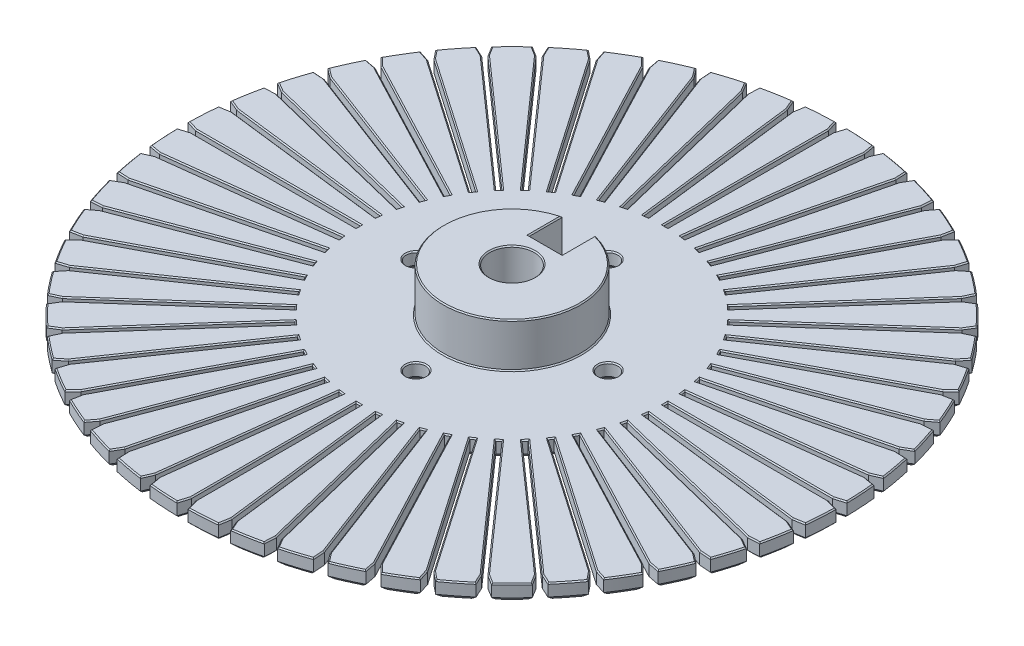
SolidWorks part; units mm, degrees
ref_plane "Ebene vorne" through (0, 0, 0) normal (0, 0, 1) x (1, 0, 0)
ref_plane "Ebene oben" through (0, 0, 0) normal (0, 1, 0) x (1, 0, 0)
ref_plane "Ebene rechts" through (0, 0, 0) normal (1, 0, 0) x (0, 0, -1)
sketch "Skizze1" plane through (0, 0, 0) normal (0, 1, 0) x (1, 0, 0)
  circle A0 centre (0, 0) radius 60
  dimension "D1" = 120
extrude "Aufsatz-Linear austragen1" add sketch "Skizze1" along normal blind 3
sketch "Skizze2" plane through (0, 3, 0) normal (0, 1, 0) x (1, 0, 0)
  line L0 (0, 0) -> (64.8042, 0) construction
  line L1 (27.9917, 0.4) -> (27.9917, -0.4)
  line L2 (27.9917, -0.4) -> (57.9917, -0.4)
  line L3 (57.9917, -0.4) -> (59.9917, -1)
  line L4 (27.9917, 0.4) -> (57.9917, 0.4)
  line L5 (57.9917, 0.4) -> (59.9917, 1)
  line L6 (0, 0) -> (64.3317, -7.8113) construction
  line L7 (27.8358, -2.9769) -> (27.7394, -3.7711)
  line L8 (27.8358, -2.9769) -> (57.6171, -6.593)
  line L9 (27.7394, -3.7711) -> (57.5206, -7.3872)
  line L10 (57.5206, -7.3872) -> (59.4337, -8.2239)
  line L11 (57.6171, -6.593) -> (59.6748, -6.2385)
  line L12 (0, 0) -> (62.9211, -15.5086) construction
  line L13 (27.274, -6.3105) -> (27.0826, -7.0872)
  line L14 (27.274, -6.3105) -> (56.4023, -13.4899)
  line L15 (27.0826, -7.0872) -> (56.2108, -14.2667)
  line L16 (56.2108, -14.2667) -> (58.0091, -15.3279)
  line L17 (56.4023, -13.4899) -> (58.4877, -13.386)
  line L18 (0, 0) -> (60.5929, -22.9799) construction
  line L19 (26.3145, -9.552) -> (26.0308, -10.3)
  line L20 (26.3145, -9.552) -> (54.365, -20.1901)
  line L21 (26.0308, -10.3) -> (54.0813, -20.9381)
  line L22 (54.0813, -20.9381) -> (55.7386, -22.2084)
  line L23 (54.365, -20.1901) -> (56.4478, -20.3383)
  line L24 (0, 0) -> (57.3812, -30.116) construction
  line L25 (24.9713, -12.6542) -> (24.5995, -13.3626)
  line L26 (24.9713, -12.6542) -> (51.535, -26.5959)
  line L27 (24.5995, -13.3626) -> (51.1632, -27.3043)
  line L28 (51.1632, -27.3043) -> (52.6553, -28.765)
  line L29 (51.535, -26.5959) -> (53.5847, -26.9941)
  line L30 (0, 0) -> (53.3328, -36.813) construction
  line L31 (23.2639, -15.5719) -> (22.8095, -16.2303)
  line L32 (23.2639, -15.5719) -> (47.9534, -32.6138)
  line L33 (22.8095, -16.2303) -> (47.499, -33.2722)
  line L34 (47.499, -33.2722) -> (48.8041, -34.9021)
  line L35 (47.9534, -32.6138) -> (49.9402, -33.2562)
  line L36 (0, 0) -> (48.5066, -42.9731) construction
  line L37 (21.2173, -18.2625) -> (20.6868, -18.8613)
  line L38 (21.2173, -18.2625) -> (43.6726, -38.1562)
  line L39 (20.6868, -18.8613) -> (43.1421, -38.755)
  line L40 (43.1421, -38.755) -> (44.2413, -40.5303)
  line L41 (43.6726, -38.1562) -> (45.5675, -39.0333)
  line L42 (0, 0) -> (42.9731, -48.5066) construction
  line L43 (18.8613, -20.6868) -> (18.2625, -21.2173)
  line L44 (18.8613, -20.6868) -> (38.755, -43.1421)
  line L45 (18.2625, -21.2173) -> (38.1562, -43.6726)
  line L46 (38.1562, -43.6726) -> (39.0333, -45.5675)
  line L47 (38.755, -43.1421) -> (40.5303, -44.2413)
  line L48 (0, 0) -> (36.813, -53.3328) construction
  line L49 (16.2303, -22.8095) -> (15.5719, -23.2639)
  line L50 (16.2303, -22.8095) -> (33.2722, -47.499)
  line L51 (15.5719, -23.2639) -> (32.6138, -47.9534)
  line L52 (32.6138, -47.9534) -> (33.2562, -49.9402)
  line L53 (33.2722, -47.499) -> (34.9021, -48.8041)
  line L54 (0, 0) -> (30.116, -57.3812) construction
  line L55 (13.3626, -24.5995) -> (12.6542, -24.9713)
  line L56 (13.3626, -24.5995) -> (27.3043, -51.1632)
  line L57 (12.6542, -24.9713) -> (26.5959, -51.535)
  line L58 (26.5959, -51.535) -> (26.9941, -53.5847)
  line L59 (27.3043, -51.1632) -> (28.765, -52.6553)
  line L60 (0, 0) -> (22.9799, -60.5929) construction
  line L61 (10.3, -26.0308) -> (9.552, -26.3145)
  line L62 (10.3, -26.0308) -> (20.9381, -54.0813)
  line L63 (9.552, -26.3145) -> (20.1901, -54.365)
  line L64 (20.1901, -54.365) -> (20.3383, -56.4478)
  line L65 (20.9381, -54.0813) -> (22.2084, -55.7386)
  line L66 (0, 0) -> (15.5086, -62.9211) construction
  line L67 (7.0872, -27.0826) -> (6.3105, -27.274)
  line L68 (7.0872, -27.0826) -> (14.2667, -56.2108)
  line L69 (6.3105, -27.274) -> (13.4899, -56.4023)
  line L70 (13.4899, -56.4023) -> (13.386, -58.4877)
  line L71 (14.2667, -56.2108) -> (15.3279, -58.0091)
  line L72 (0, 0) -> (7.8113, -64.3317) construction
  line L73 (3.7711, -27.7394) -> (2.9769, -27.8358)
  line L74 (3.7711, -27.7394) -> (7.3872, -57.5206)
  line L75 (2.9769, -27.8358) -> (6.593, -57.6171)
  line L76 (6.593, -57.6171) -> (6.2385, -59.6748)
  line L77 (7.3872, -57.5206) -> (8.2239, -59.4337)
  line L78 (0, 0) -> (0, -64.8042) construction
  line L79 (0.4, -27.9917) -> (-0.4, -27.9917)
  line L80 (0.4, -27.9917) -> (0.4, -57.9917)
  line L81 (-0.4, -27.9917) -> (-0.4, -57.9917)
  line L82 (-0.4, -57.9917) -> (-1, -59.9917)
  line L83 (0.4, -57.9917) -> (1, -59.9917)
  line L84 (0, 0) -> (-7.8113, -64.3317) construction
  line L85 (-2.9769, -27.8358) -> (-3.7711, -27.7394)
  line L86 (-2.9769, -27.8358) -> (-6.593, -57.6171)
  line L87 (-3.7711, -27.7394) -> (-7.3872, -57.5206)
  line L88 (-7.3872, -57.5206) -> (-8.2239, -59.4337)
  line L89 (-6.593, -57.6171) -> (-6.2385, -59.6748)
  line L90 (0, 0) -> (-15.5086, -62.9211) construction
  line L91 (-6.3105, -27.274) -> (-7.0872, -27.0826)
  line L92 (-6.3105, -27.274) -> (-13.4899, -56.4023)
  line L93 (-7.0872, -27.0826) -> (-14.2667, -56.2108)
  line L94 (-14.2667, -56.2108) -> (-15.3279, -58.0091)
  line L95 (-13.4899, -56.4023) -> (-13.386, -58.4877)
  line L96 (0, 0) -> (-22.9799, -60.5929) construction
  line L97 (-9.552, -26.3145) -> (-10.3, -26.0308)
  line L98 (-9.552, -26.3145) -> (-20.1901, -54.365)
  line L99 (-10.3, -26.0308) -> (-20.9381, -54.0813)
  line L100 (-20.9381, -54.0813) -> (-22.2084, -55.7386)
  line L101 (-20.1901, -54.365) -> (-20.3383, -56.4478)
  line L102 (0, 0) -> (-30.116, -57.3812) construction
  line L103 (-12.6542, -24.9713) -> (-13.3626, -24.5995)
  line L104 (-12.6542, -24.9713) -> (-26.5959, -51.535)
  line L105 (-13.3626, -24.5995) -> (-27.3043, -51.1632)
  line L106 (-27.3043, -51.1632) -> (-28.765, -52.6553)
  line L107 (-26.5959, -51.535) -> (-26.9941, -53.5847)
  line L108 (0, 0) -> (-36.813, -53.3328) construction
  line L109 (-15.5719, -23.2639) -> (-16.2303, -22.8095)
  line L110 (-15.5719, -23.2639) -> (-32.6138, -47.9534)
  line L111 (-16.2303, -22.8095) -> (-33.2722, -47.499)
  line L112 (-33.2722, -47.499) -> (-34.9021, -48.8041)
  line L113 (-32.6138, -47.9534) -> (-33.2562, -49.9402)
  line L114 (0, 0) -> (-42.9731, -48.5066) construction
  line L115 (-18.2625, -21.2173) -> (-18.8613, -20.6868)
  line L116 (-18.2625, -21.2173) -> (-38.1562, -43.6726)
  line L117 (-18.8613, -20.6868) -> (-38.755, -43.1421)
  line L118 (-38.755, -43.1421) -> (-40.5303, -44.2413)
  line L119 (-38.1562, -43.6726) -> (-39.0333, -45.5675)
  line L120 (0, 0) -> (-48.5066, -42.9731) construction
  line L121 (-20.6868, -18.8613) -> (-21.2173, -18.2625)
  line L122 (-20.6868, -18.8613) -> (-43.1421, -38.755)
  line L123 (-21.2173, -18.2625) -> (-43.6726, -38.1562)
  line L124 (-43.6726, -38.1562) -> (-45.5675, -39.0333)
  line L125 (-43.1421, -38.755) -> (-44.2413, -40.5303)
  line L126 (0, 0) -> (-53.3328, -36.813) construction
  line L127 (-22.8095, -16.2303) -> (-23.2639, -15.5719)
  line L128 (-22.8095, -16.2303) -> (-47.499, -33.2722)
  line L129 (-23.2639, -15.5719) -> (-47.9534, -32.6138)
  line L130 (-47.9534, -32.6138) -> (-49.9402, -33.2562)
  line L131 (-47.499, -33.2722) -> (-48.8041, -34.9021)
  line L132 (0, 0) -> (-57.3812, -30.116) construction
  line L133 (-24.5995, -13.3626) -> (-24.9713, -12.6542)
  line L134 (-24.5995, -13.3626) -> (-51.1632, -27.3043)
  line L135 (-24.9713, -12.6542) -> (-51.535, -26.5959)
  line L136 (-51.535, -26.5959) -> (-53.5847, -26.9941)
  line L137 (-51.1632, -27.3043) -> (-52.6553, -28.765)
  line L138 (0, 0) -> (-60.5929, -22.9799) construction
  line L139 (-26.0308, -10.3) -> (-26.3145, -9.552)
  line L140 (-26.0308, -10.3) -> (-54.0813, -20.9381)
  line L141 (-26.3145, -9.552) -> (-54.365, -20.1901)
  line L142 (-54.365, -20.1901) -> (-56.4478, -20.3383)
  line L143 (-54.0813, -20.9381) -> (-55.7386, -22.2084)
  line L144 (0, 0) -> (-62.9211, -15.5086) construction
  line L145 (-27.0826, -7.0872) -> (-27.274, -6.3105)
  line L146 (-27.0826, -7.0872) -> (-56.2108, -14.2667)
  line L147 (-27.274, -6.3105) -> (-56.4023, -13.4899)
  line L148 (-56.4023, -13.4899) -> (-58.4877, -13.386)
  line L149 (-56.2108, -14.2667) -> (-58.0091, -15.3279)
  line L150 (0, 0) -> (-64.3317, -7.8113) construction
  line L151 (-27.7394, -3.7711) -> (-27.8358, -2.9769)
  line L152 (-27.7394, -3.7711) -> (-57.5206, -7.3872)
  line L153 (-27.8358, -2.9769) -> (-57.6171, -6.593)
  line L154 (-57.6171, -6.593) -> (-59.6748, -6.2385)
  line L155 (-57.5206, -7.3872) -> (-59.4337, -8.2239)
  line L156 (0, 0) -> (-64.8042, 0) construction
  line L157 (-27.9917, -0.4) -> (-27.9917, 0.4)
  line L158 (-27.9917, -0.4) -> (-57.9917, -0.4)
  line L159 (-27.9917, 0.4) -> (-57.9917, 0.4)
  line L160 (-57.9917, 0.4) -> (-59.9917, 1)
  line L161 (-57.9917, -0.4) -> (-59.9917, -1)
  line L162 (0, 0) -> (-64.3317, 7.8113) construction
  line L163 (-27.8358, 2.9769) -> (-27.7394, 3.7711)
  line L164 (-27.8358, 2.9769) -> (-57.6171, 6.593)
  line L165 (-27.7394, 3.7711) -> (-57.5206, 7.3872)
  line L166 (-57.5206, 7.3872) -> (-59.4337, 8.2239)
  line L167 (-57.6171, 6.593) -> (-59.6748, 6.2385)
  line L168 (0, 0) -> (-62.9211, 15.5086) construction
  line L169 (-27.274, 6.3105) -> (-27.0826, 7.0872)
  line L170 (-27.274, 6.3105) -> (-56.4023, 13.4899)
  line L171 (-27.0826, 7.0872) -> (-56.2108, 14.2667)
  line L172 (-56.2108, 14.2667) -> (-58.0091, 15.3279)
  line L173 (-56.4023, 13.4899) -> (-58.4877, 13.386)
  line L174 (0, 0) -> (-60.5929, 22.9799) construction
  line L175 (-26.3145, 9.552) -> (-26.0308, 10.3)
  line L176 (-26.3145, 9.552) -> (-54.365, 20.1901)
  line L177 (-26.0308, 10.3) -> (-54.0813, 20.9381)
  line L178 (-54.0813, 20.9381) -> (-55.7386, 22.2084)
  line L179 (-54.365, 20.1901) -> (-56.4478, 20.3383)
  line L180 (0, 0) -> (-57.3812, 30.116) construction
  line L181 (-24.9713, 12.6542) -> (-24.5995, 13.3626)
  line L182 (-24.9713, 12.6542) -> (-51.535, 26.5959)
  line L183 (-24.5995, 13.3626) -> (-51.1632, 27.3043)
  line L184 (-51.1632, 27.3043) -> (-52.6553, 28.765)
  line L185 (-51.535, 26.5959) -> (-53.5847, 26.9941)
  line L186 (0, 0) -> (-53.3328, 36.813) construction
  line L187 (-23.2639, 15.5719) -> (-22.8095, 16.2303)
  line L188 (-23.2639, 15.5719) -> (-47.9534, 32.6138)
  line L189 (-22.8095, 16.2303) -> (-47.499, 33.2722)
  line L190 (-47.499, 33.2722) -> (-48.8041, 34.9021)
  line L191 (-47.9534, 32.6138) -> (-49.9402, 33.2562)
  line L192 (0, 0) -> (-48.5066, 42.9731) construction
  line L193 (-21.2173, 18.2625) -> (-20.6868, 18.8613)
  line L194 (-21.2173, 18.2625) -> (-43.6726, 38.1562)
  line L195 (-20.6868, 18.8613) -> (-43.1421, 38.755)
  line L196 (-43.1421, 38.755) -> (-44.2413, 40.5303)
  line L197 (-43.6726, 38.1562) -> (-45.5675, 39.0333)
  line L198 (0, 0) -> (-42.9731, 48.5066) construction
  line L199 (-18.8613, 20.6868) -> (-18.2625, 21.2173)
  line L200 (-18.8613, 20.6868) -> (-38.755, 43.1421)
  line L201 (-18.2625, 21.2173) -> (-38.1562, 43.6726)
  line L202 (-38.1562, 43.6726) -> (-39.0333, 45.5675)
  line L203 (-38.755, 43.1421) -> (-40.5303, 44.2413)
  line L204 (0, 0) -> (-36.813, 53.3328) construction
  line L205 (-16.2303, 22.8095) -> (-15.5719, 23.2639)
  line L206 (-16.2303, 22.8095) -> (-33.2722, 47.499)
  line L207 (-15.5719, 23.2639) -> (-32.6138, 47.9534)
  line L208 (-32.6138, 47.9534) -> (-33.2562, 49.9402)
  line L209 (-33.2722, 47.499) -> (-34.9021, 48.8041)
  line L210 (0, 0) -> (-30.116, 57.3812) construction
  line L211 (-13.3626, 24.5995) -> (-12.6542, 24.9713)
  line L212 (-13.3626, 24.5995) -> (-27.3043, 51.1632)
  line L213 (-12.6542, 24.9713) -> (-26.5959, 51.535)
  line L214 (-26.5959, 51.535) -> (-26.9941, 53.5847)
  line L215 (-27.3043, 51.1632) -> (-28.765, 52.6553)
  line L216 (0, 0) -> (-22.9799, 60.5929) construction
  line L217 (-10.3, 26.0308) -> (-9.552, 26.3145)
  line L218 (-10.3, 26.0308) -> (-20.9381, 54.0813)
  line L219 (-9.552, 26.3145) -> (-20.1901, 54.365)
  line L220 (-20.1901, 54.365) -> (-20.3383, 56.4478)
  line L221 (-20.9381, 54.0813) -> (-22.2084, 55.7386)
  line L222 (0, 0) -> (-15.5086, 62.9211) construction
  line L223 (-7.0872, 27.0826) -> (-6.3105, 27.274)
  line L224 (-7.0872, 27.0826) -> (-14.2667, 56.2108)
  line L225 (-6.3105, 27.274) -> (-13.4899, 56.4023)
  line L226 (-13.4899, 56.4023) -> (-13.386, 58.4877)
  line L227 (-14.2667, 56.2108) -> (-15.3279, 58.0091)
  line L228 (0, 0) -> (-7.8113, 64.3317) construction
  line L229 (-3.7711, 27.7394) -> (-2.9769, 27.8358)
  line L230 (-3.7711, 27.7394) -> (-7.3872, 57.5206)
  line L231 (-2.9769, 27.8358) -> (-6.593, 57.6171)
  line L232 (-6.593, 57.6171) -> (-6.2385, 59.6748)
  line L233 (-7.3872, 57.5206) -> (-8.2239, 59.4337)
  line L234 (0, 0) -> (0, 64.8042) construction
  line L235 (-0.4, 27.9917) -> (0.4, 27.9917)
  line L236 (-0.4, 27.9917) -> (-0.4, 57.9917)
  line L237 (0.4, 27.9917) -> (0.4, 57.9917)
  line L238 (0.4, 57.9917) -> (1, 59.9917)
  line L239 (-0.4, 57.9917) -> (-1, 59.9917)
  line L240 (0, 0) -> (7.8113, 64.3317) construction
  line L241 (2.9769, 27.8358) -> (3.7711, 27.7394)
  line L242 (2.9769, 27.8358) -> (6.593, 57.6171)
  line L243 (3.7711, 27.7394) -> (7.3872, 57.5206)
  line L244 (7.3872, 57.5206) -> (8.2239, 59.4337)
  line L245 (6.593, 57.6171) -> (6.2385, 59.6748)
  line L246 (0, 0) -> (15.5086, 62.9211) construction
  line L247 (6.3105, 27.274) -> (7.0872, 27.0826)
  line L248 (6.3105, 27.274) -> (13.4899, 56.4023)
  line L249 (7.0872, 27.0826) -> (14.2667, 56.2108)
  line L250 (14.2667, 56.2108) -> (15.3279, 58.0091)
  line L251 (13.4899, 56.4023) -> (13.386, 58.4877)
  line L252 (0, 0) -> (22.9799, 60.5929) construction
  line L253 (9.552, 26.3145) -> (10.3, 26.0308)
  line L254 (9.552, 26.3145) -> (20.1901, 54.365)
  line L255 (10.3, 26.0308) -> (20.9381, 54.0813)
  line L256 (20.9381, 54.0813) -> (22.2084, 55.7386)
  line L257 (20.1901, 54.365) -> (20.3383, 56.4478)
  line L258 (0, 0) -> (30.116, 57.3812) construction
  line L259 (12.6542, 24.9713) -> (13.3626, 24.5995)
  line L260 (12.6542, 24.9713) -> (26.5959, 51.535)
  line L261 (13.3626, 24.5995) -> (27.3043, 51.1632)
  line L262 (27.3043, 51.1632) -> (28.765, 52.6553)
  line L263 (26.5959, 51.535) -> (26.9941, 53.5847)
  line L264 (0, 0) -> (36.813, 53.3328) construction
  line L265 (15.5719, 23.2639) -> (16.2303, 22.8095)
  line L266 (15.5719, 23.2639) -> (32.6138, 47.9534)
  line L267 (16.2303, 22.8095) -> (33.2722, 47.499)
  line L268 (33.2722, 47.499) -> (34.9021, 48.8041)
  line L269 (32.6138, 47.9534) -> (33.2562, 49.9402)
  line L270 (0, 0) -> (42.9731, 48.5066) construction
  line L271 (18.2625, 21.2173) -> (18.8613, 20.6868)
  line L272 (18.2625, 21.2173) -> (38.1562, 43.6726)
  line L273 (18.8613, 20.6868) -> (38.755, 43.1421)
  line L274 (38.755, 43.1421) -> (40.5303, 44.2413)
  line L275 (38.1562, 43.6726) -> (39.0333, 45.5675)
  line L276 (0, 0) -> (48.5066, 42.9731) construction
  line L277 (20.6868, 18.8613) -> (21.2173, 18.2625)
  line L278 (20.6868, 18.8613) -> (43.1421, 38.755)
  line L279 (21.2173, 18.2625) -> (43.6726, 38.1562)
  line L280 (43.6726, 38.1562) -> (45.5675, 39.0333)
  line L281 (43.1421, 38.755) -> (44.2413, 40.5303)
  line L282 (0, 0) -> (53.3328, 36.813) construction
  line L283 (22.8095, 16.2303) -> (23.2639, 15.5719)
  line L284 (22.8095, 16.2303) -> (47.499, 33.2722)
  line L285 (23.2639, 15.5719) -> (47.9534, 32.6138)
  line L286 (47.9534, 32.6138) -> (49.9402, 33.2562)
  line L287 (47.499, 33.2722) -> (48.8041, 34.9021)
  line L288 (0, 0) -> (57.3812, 30.116) construction
  line L289 (24.5995, 13.3626) -> (24.9713, 12.6542)
  line L290 (24.5995, 13.3626) -> (51.1632, 27.3043)
  line L291 (24.9713, 12.6542) -> (51.535, 26.5959)
  line L292 (51.535, 26.5959) -> (53.5847, 26.9941)
  line L293 (51.1632, 27.3043) -> (52.6553, 28.765)
  line L294 (0, 0) -> (60.5929, 22.9799) construction
  line L295 (26.0308, 10.3) -> (26.3145, 9.552)
  line L296 (26.0308, 10.3) -> (54.0813, 20.9381)
  line L297 (26.3145, 9.552) -> (54.365, 20.1901)
  line L298 (54.365, 20.1901) -> (56.4478, 20.3383)
  line L299 (54.0813, 20.9381) -> (55.7386, 22.2084)
  line L300 (0, 0) -> (62.9211, 15.5086) construction
  line L301 (27.0826, 7.0872) -> (27.274, 6.3105)
  line L302 (27.0826, 7.0872) -> (56.2108, 14.2667)
  line L303 (27.274, 6.3105) -> (56.4023, 13.4899)
  line L304 (56.4023, 13.4899) -> (58.4877, 13.386)
  line L305 (56.2108, 14.2667) -> (58.0091, 15.3279)
  line L306 (0, 0) -> (64.3317, 7.8113) construction
  line L307 (27.7394, 3.7711) -> (27.8358, 2.9769)
  line L308 (27.7394, 3.7711) -> (57.5206, 7.3872)
  line L309 (27.8358, 2.9769) -> (57.6171, 6.593)
  line L310 (57.6171, 6.593) -> (59.6748, 6.2385)
  line L311 (57.5206, 7.3872) -> (59.4337, 8.2239)
  arc A0 (59.9917, 1) -> (59.9917, -1) centre (0, 0) cw
  circle A1 centre (0, 0) radius 60 construction
  arc A2 (59.6748, -6.2385) -> (59.4337, -8.2239) centre (0, 0) cw
  arc A3 (58.4877, -13.386) -> (58.0091, -15.3279) centre (0, 0) cw
  arc A4 (56.4478, -20.3383) -> (55.7386, -22.2084) centre (0, 0) cw
  arc A5 (53.5847, -26.9941) -> (52.6553, -28.765) centre (0, 0) cw
  arc A6 (49.9402, -33.2562) -> (48.8041, -34.9021) centre (0, 0) cw
  arc A7 (45.5675, -39.0333) -> (44.2413, -40.5303) centre (0, 0) cw
  arc A8 (40.5303, -44.2413) -> (39.0333, -45.5675) centre (0, 0) cw
  arc A9 (34.9021, -48.8041) -> (33.2562, -49.9402) centre (0, 0) cw
  arc A10 (28.765, -52.6553) -> (26.9941, -53.5847) centre (0, 0) cw
  arc A11 (22.2084, -55.7386) -> (20.3383, -56.4478) centre (0, 0) cw
  arc A12 (15.3279, -58.0091) -> (13.386, -58.4877) centre (0, 0) cw
  arc A13 (8.2239, -59.4337) -> (6.2385, -59.6748) centre (0, 0) cw
  arc A14 (1, -59.9917) -> (-1, -59.9917) centre (0, 0) cw
  arc A15 (-6.2385, -59.6748) -> (-8.2239, -59.4337) centre (0, 0) cw
  arc A16 (-13.386, -58.4877) -> (-15.3279, -58.0091) centre (0, 0) cw
  arc A17 (-20.3383, -56.4478) -> (-22.2084, -55.7386) centre (0, 0) cw
  arc A18 (-26.9941, -53.5847) -> (-28.765, -52.6553) centre (0, 0) cw
  arc A19 (-33.2562, -49.9402) -> (-34.9021, -48.8041) centre (0, 0) cw
  arc A20 (-39.0333, -45.5675) -> (-40.5303, -44.2413) centre (0, 0) cw
  arc A21 (-44.2413, -40.5303) -> (-45.5675, -39.0333) centre (0, 0) cw
  arc A22 (-48.8041, -34.9021) -> (-49.9402, -33.2562) centre (0, 0) cw
  arc A23 (-52.6553, -28.765) -> (-53.5847, -26.9941) centre (0, 0) cw
  arc A24 (-55.7386, -22.2084) -> (-56.4478, -20.3383) centre (0, 0) cw
  arc A25 (-58.0091, -15.3279) -> (-58.4877, -13.386) centre (0, 0) cw
  arc A26 (-59.4337, -8.2239) -> (-59.6748, -6.2385) centre (0, 0) cw
  arc A27 (-59.9917, -1) -> (-59.9917, 1) centre (0, 0) cw
  arc A28 (-59.6748, 6.2385) -> (-59.4337, 8.2239) centre (0, 0) cw
  arc A29 (-58.4877, 13.386) -> (-58.0091, 15.3279) centre (0, 0) cw
  arc A30 (-56.4478, 20.3383) -> (-55.7386, 22.2084) centre (0, 0) cw
  arc A31 (-53.5847, 26.9941) -> (-52.6553, 28.765) centre (0, 0) cw
  arc A32 (-49.9402, 33.2562) -> (-48.8041, 34.9021) centre (0, 0) cw
  arc A33 (-45.5675, 39.0333) -> (-44.2413, 40.5303) centre (0, 0) cw
  arc A34 (-40.5303, 44.2413) -> (-39.0333, 45.5675) centre (0, 0) cw
  arc A35 (-34.9021, 48.8041) -> (-33.2562, 49.9402) centre (0, 0) cw
  arc A36 (-28.765, 52.6553) -> (-26.9941, 53.5847) centre (0, 0) cw
  arc A37 (-22.2084, 55.7386) -> (-20.3383, 56.4478) centre (0, 0) cw
  arc A38 (-15.3279, 58.0091) -> (-13.386, 58.4877) centre (0, 0) cw
  arc A39 (-8.2239, 59.4337) -> (-6.2385, 59.6748) centre (0, 0) cw
  arc A40 (-1, 59.9917) -> (1, 59.9917) centre (0, 0) cw
  arc A41 (6.2385, 59.6748) -> (8.2239, 59.4337) centre (0, 0) cw
  arc A42 (13.386, 58.4877) -> (15.3279, 58.0091) centre (0, 0) cw
  arc A43 (20.3383, 56.4478) -> (22.2084, 55.7386) centre (0, 0) cw
  arc A44 (26.9941, 53.5847) -> (28.765, 52.6553) centre (0, 0) cw
  arc A45 (33.2562, 49.9402) -> (34.9021, 48.8041) centre (0, 0) cw
  arc A46 (39.0333, 45.5675) -> (40.5303, 44.2413) centre (0, 0) cw
  arc A47 (44.2413, 40.5303) -> (45.5675, 39.0333) centre (0, 0) cw
  arc A48 (48.8041, 34.9021) -> (49.9402, 33.2562) centre (0, 0) cw
  arc A49 (52.6553, 28.765) -> (53.5847, 26.9941) centre (0, 0) cw
  arc A50 (55.7386, 22.2084) -> (56.4478, 20.3383) centre (0, 0) cw
  arc A51 (58.0091, 15.3279) -> (58.4877, 13.386) centre (0, 0) cw
  arc A52 (59.4337, 8.2239) -> (59.6748, 6.2385) centre (0, 0) cw
  point P373 (0, 0)
  dimension "D5" = 52
  dimension "D1" = 0.8
  dimension "D2" = 30
  dimension "D3" = 2
  dimension "D4" = 2
extrude "Schnitt-Linear austragen1" cut sketch "Skizze2" against normal blind 5
sketch "Skizze3" plane through (0, 3, 0) normal (0, 1, 0) x (1, 0, 0)
  line L0 (0, 12.5) -> (0, 0) construction
  line L7 (-3, 12.1347) -> (-3, 6.1347)
  line L8 (-3, 6.1347) -> (3, 6.1347)
  line L9 (3, 6.1347) -> (3, 12.1347)
  arc A0 (-3, 12.1347) -> (3, 12.1347) centre (0, 0) ccw
  dimension "D1" = 25
  dimension "D2" = 6
  dimension "D3" = 6
extrude "Aufsatz-Linear austragen2" add sketch "Skizze3" along normal blind 8
sketch "Skizze4" plane through (0, 11, 0) normal (0, 1, 0) x (1, 0, 0)
  circle A0 centre (0, 0) radius 4.05
  dimension "D1" = 8.1
extrude "Schnitt-Linear austragen4" cut sketch "Skizze4" against normal through all
sketch "Skizze5" plane through (0, 3, 0) normal (0, 1, 0) x (1, 0, 0)
  circle A0 centre (0, 0) radius 17.5 construction
  circle A1 centre (0, 17.5) radius 1.75
  circle A2 centre (17.5, 0) radius 1.75
  circle A3 centre (-17.5, 0) radius 1.75
  circle A4 centre (0, -17.5) radius 1.75
  dimension "D1" = 3.5
  dimension "D2" = 35
extrude "Schnitt-Linear austragen5" cut sketch "Skizze5" against normal up to surface (3 mm away) up to face at (0, 0, 4.05)
chamfer "Fase1" distance 0.8 angle 45 317 edges at (27.7876, 0, -3.374) (42.63, 0, -5.5792) (58.4772, 0, -7.8056) (59.0172, 0, -10.8153) (57.445, 0, -13.438) (41.8381, 0, -9.9002) (27.1783, 0, -6.6988) (41.6467, 0, -10.677) (57.11, 0, -14.7973) (57.2833, 0, -17.8502) (55.4064, 0, -20.2642) (40.3397, 0, -14.871) (26.1727, 0, -9.926) (40.0561, 0, -15.6191) (54.9099, 0, -21.5732) (54.714, 0, -24.6248) (52.5598, 0, -26.795) (38.2531, 0, -19.625) (24.7854, 0, -13.0084) (37.8813, 0, -20.3334) (51.9092, 0, -28.0346) (51.3469, 0, -31.0403) (48.9468, 0, -32.935) (35.6087, 0, -24.0929) (23.0367, 0, -15.9011) (35.1542, 0, -24.7512) (48.1515, 0, -34.0872) (47.231, 0, -37.0031) (44.6201, 0, -38.5948) (32.445, 0, -28.2093) (20.9521, 0, -18.5619) (31.9145, 0, -28.8082) (43.6917, 0, -39.6427) (42.4264, 0, -42.4264) (39.6427, 0, -43.6917) (28.8082, 0, -31.9145) (18.5619, 0, -20.9521) (28.2093, 0, -32.445) (38.5948, 0, -44.6201) (37.0031, 0, -47.231) (34.0872, 0, -48.1515) (24.7512, 0, -35.1542) (15.9011, 0, -23.0367) (24.0929, 0, -35.6087) (32.935, 0, -48.9468) (31.0403, 0, -51.3469) (28.0346, 0, -51.9092) (20.3334, 0, -37.8813) (13.0084, 0, -24.7854) (19.625, 0, -38.2531) (26.795, 0, -52.5598) (24.6248, 0, -54.714) (21.5732, 0, -54.9099) (15.6191, 0, -40.0561) (9.926, 0, -26.1727) (14.871, 0, -40.3397) (20.2642, 0, -55.4064) (17.8502, 0, -57.2833) (14.7973, 0, -57.11) (10.677, 0, -41.6467) (6.6988, 0, -27.1783) (9.9002, 0, -41.8381) (13.438, 0, -57.445) (10.8153, 0, -59.0172) (7.8056, 0, -58.4772) (5.5792, 0, -42.63) (3.374, 0, -27.7876) (4.785, 0, -42.7264) (6.4158, 0, -58.6459) (3.6227, 0, -59.8905) (0.7, 0, -58.9917) (0.4, 0, -42.9917) (0, 0, -27.9917) (-0.4, 0, -42.9917) (-0.7, 0, -58.9917) (-3.6227, 0, -59.8905) (-6.4158, 0, -58.6459) (-4.785, 0, -42.7264) (-3.374, 0, -27.7876) (-5.5792, 0, -42.63) (-7.8056, 0, -58.4772) (-10.8153, 0, -59.0172) (-13.438, 0, -57.445) (-9.9002, 0, -41.8381) (-6.6988, 0, -27.1783) (-10.677, 0, -41.6467) (-14.7973, 0, -57.11) (-17.8502, 0, -57.2833) (-20.2642, 0, -55.4064) (-14.871, 0, -40.3397) (-9.926, 0, -26.1727) (-15.6191, 0, -40.0561) (-21.5732, 0, -54.9099) (-24.6248, 0, -54.714) (-26.795, 0, -52.5598) (-19.625, 0, -38.2531) (-13.0084, 0, -24.7854) (-20.3334, 0, -37.8813) (-28.0346, 0, -51.9092) (-31.0403, 0, -51.3469) (-32.935, 0, -48.9468) (-24.0929, 0, -35.6087) (-15.9011, 0, -23.0367) (-24.7512, 0, -35.1542) (-34.0872, 0, -48.1515) (-37.0031, 0, -47.231) (-38.5948, 0, -44.6201) (-28.2093, 0, -32.445) (-18.5619, 0, -20.9521) (-28.8082, 0, -31.9145) (-39.6427, 0, -43.6917) (-42.4264, 0, -42.4264) (-43.6917, 0, -39.6427) (-31.9145, 0, -28.8082) (-20.9521, 0, -18.5619) (-32.445, 0, -28.2093) (-44.6201, 0, -38.5948) (-47.231, 0, -37.0031) (-48.1515, 0, -34.0872) (-35.1542, 0, -24.7512) (-23.0367, 0, -15.9011) (-35.6087, 0, -24.0929) (-48.9468, 0, -32.935) (-51.3469, 0, -31.0403) (-51.9092, 0, -28.0346) (-37.8813, 0, -20.3334) (-24.7854, 0, -13.0084) (-38.2531, 0, -19.625) (-52.5598, 0, -26.795) (-54.714, 0, -24.6248) (-54.9099, 0, -21.5732) (-40.0561, 0, -15.6191) (-26.1727, 0, -9.926) (-40.3397, 0, -14.871) (-55.4064, 0, -20.2642) (-57.2833, 0, -17.8502) (-57.11, 0, -14.7973) (-41.6467, 0, -10.677) (-27.1783, 0, -6.6988) (-41.8381, 0, -9.9002) (-57.445, 0, -13.438) (-59.0172, 0, -10.8153) (-58.4772, 0, -7.8056) (-42.63, 0, -5.5792) (-27.7876, 0, -3.374) (-42.7264, 0, -4.785) (-58.6459, 0, -6.4158) (-59.8905, 0, -3.6227) (-58.9917, 0, -0.7) (-42.9917, 0, -0.4) (-27.9917, 0, 0) (-42.9917, 0, 0.4) (-58.9917, 0, 0.7) (-59.8905, 0, 3.6227) (-58.6459, 0, 6.4158) (-42.7264, 0, 4.785) (-27.7876, 0, 3.374) (-42.63, 0, 5.5792) (-58.4772, 0, 7.8056) (-59.0172, 0, 10.8153) (-57.445, 0, 13.438) (-41.8381, 0, 9.9002) (-27.1783, 0, 6.6988) (-41.6467, 0, 10.677) (-57.11, 0, 14.7973) (-57.2833, 0, 17.8502) (-55.4064, 0, 20.2642) (-40.3397, 0, 14.871) (-26.1727, 0, 9.926) (-40.0561, 0, 15.6191) (-54.9099, 0, 21.5732) (-54.714, 0, 24.6248) (-52.5598, 0, 26.795) (-38.2531, 0, 19.625) (-24.7854, 0, 13.0084) (-37.8813, 0, 20.3334) (-51.9092, 0, 28.0346) (-51.3469, 0, 31.0403) (-48.9468, 0, 32.935) (-35.6087, 0, 24.0929) (-23.0367, 0, 15.9011) (-35.1542, 0, 24.7512) (-48.1515, 0, 34.0872) (-47.231, 0, 37.0031) (-44.6201, 0, 38.5948) (-32.445, 0, 28.2093) (-20.9521, 0, 18.5619) (-31.9145, 0, 28.8082) (-43.6917, 0, 39.6427) (-42.4264, 0, 42.4264) (-39.6427, 0, 43.6917) (-28.8082, 0, 31.9145) (-18.5619, 0, 20.9521) (-28.2093, 0, 32.445) (-38.5948, 0, 44.6201) (-37.0031, 0, 47.231) (-34.0872, 0, 48.1515) (-24.7512, 0, 35.1542) (-15.9011, 0, 23.0367) (-24.0929, 0, 35.6087) (-32.935, 0, 48.9468) (-31.0403, 0, 51.3469) (-28.0346, 0, 51.9092) (-20.3334, 0, 37.8813) (-13.0084, 0, 24.7854) (-19.625, 0, 38.2531) (-26.795, 0, 52.5598) (-24.6248, 0, 54.714) (-21.5732, 0, 54.9099) (-15.6191, 0, 40.0561) (-9.926, 0, 26.1727) (-14.871, 0, 40.3397) (-20.2642, 0, 55.4064) (-17.8502, 0, 57.2833) (-14.7973, 0, 57.11) (-10.677, 0, 41.6467) (-6.6988, 0, 27.1783) (-9.9002, 0, 41.8381) (-13.438, 0, 57.445) (-10.8153, 0, 59.0172) (-7.8056, 0, 58.4772) (-5.5792, 0, 42.63) (-3.374, 0, 27.7876) (-4.785, 0, 42.7264) (-6.4158, 0, 58.6459) (-3.6227, 0, 59.8905) (-0.7, 0, 58.9917) (-0.4, 0, 42.9917) (0, 0, 27.9917) (0.4, 0, 42.9917) (0.7, 0, 58.9917) (3.6227, 0, 59.8905) (6.4158, 0, 58.6459) (4.785, 0, 42.7264) (3.374, 0, 27.7876) (5.5792, 0, 42.63) (7.8056, 0, 58.4772) (10.8153, 0, 59.0172) (13.438, 0, 57.445) (9.9002, 0, 41.8381) (6.6988, 0, 27.1783) (10.677, 0, 41.6467) (14.7973, 0, 57.11) (17.8502, 0, 57.2833) (20.2642, 0, 55.4064) (14.871, 0, 40.3397) (9.926, 0, 26.1727) (15.6191, 0, 40.0561) (21.5732, 0, 54.9099) (24.6248, 0, 54.714) (26.795, 0, 52.5598) (19.625, 0, 38.2531) (13.0084, 0, 24.7854) (20.3334, 0, 37.8813) (28.0346, 0, 51.9092) (31.0403, 0, 51.3469) (32.935, 0, 48.9468) (24.0929, 0, 35.6087) (15.9011, 0, 23.0367) (24.7512, 0, 35.1542) (34.0872, 0, 48.1515) (37.0031, 0, 47.231) (38.5948, 0, 44.6201) (28.2093, 0, 32.445) (18.5619, 0, 20.9521) (28.8082, 0, 31.9145) (39.6427, 0, 43.6917) (42.4264, 0, 42.4264) (43.6917, 0, 39.6427) (31.9145, 0, 28.8082) (20.9521, 0, 18.5619) (32.445, 0, 28.2093) (44.6201, 0, 38.5948) (47.231, 0, 37.0031) (48.1515, 0, 34.0872) (35.1542, 0, 24.7512) (23.0367, 0, 15.9011) (35.6087, 0, 24.0929) (48.9468, 0, 32.935) (51.3469, 0, 31.0403) (51.9092, 0, 28.0346) (37.8813, 0, 20.3334) (24.7854, 0, 13.0084) (38.2531, 0, 19.625) (52.5598, 0, 26.795) (54.714, 0, 24.6248) (54.9099, 0, 21.5732) (40.0561, 0, 15.6191) (26.1727, 0, 9.926) (40.3397, 0, 14.871) (55.4064, 0, 20.2642) (57.2833, 0, 17.8502) (57.11, 0, 14.7973) (41.6467, 0, 10.677) (27.1783, 0, 6.6988) (41.8381, 0, 9.9002) (57.445, 0, 13.438) (59.0172, 0, 10.8153) (58.4772, 0, 7.8056) (42.63, 0, 5.5792) (27.7876, 0, 3.374) (42.7264, 0, 4.785) (58.6459, 0, 6.4158) (59.8905, 0, 3.6227) (58.9917, 0, 0.7) (42.9917, 0, 0.4) (27.9917, 0, 0) (42.9917, 0, -0.4) (58.9917, 0, -0.7) (59.8905, 0, -3.6227) (58.6459, 0, -6.4158) (42.7264, 0, -4.785) (0, 0, 4.05) (0, 0, -15.75) (17.5, 0, 1.75) (-17.5, 0, 1.75) (0, 0, 19.25)
chamfer "Fase2" distance 0.2 angle 45 325 edges at (-3, 11, -9.1347) (0, 11, -6.1347) (3, 11, -9.1347) (0, 11, 12.5) (0, 11, 4.05) (0, 3, -6.1347) (-3, 3, -9.1347) (0, 3, 12.5) (3, 3, -9.1347) (59.8905, 3, -3.6227) (58.9917, 3, -0.7) (42.9917, 3, -0.4) (27.9917, 3, 0) (42.9917, 3, 0.4) (58.9917, 3, 0.7) (59.8905, 3, 3.6227) (58.6459, 3, 6.4158) (42.7264, 3, 4.785) (27.7876, 3, 3.374) (42.63, 3, 5.5792) (58.4772, 3, 7.8056) (59.0172, 3, 10.8153) (57.445, 3, 13.438) (41.8381, 3, 9.9002) (27.1783, 3, 6.6988) (41.6467, 3, 10.677) (57.11, 3, 14.7973) (57.2833, 3, 17.8502) (55.4064, 3, 20.2642) (40.3397, 3, 14.871) (26.1727, 3, 9.926) (40.0561, 3, 15.6191) (54.9099, 3, 21.5732) (54.714, 3, 24.6248) (52.5598, 3, 26.795) (38.2531, 3, 19.625) (24.7854, 3, 13.0084) (37.8813, 3, 20.3334) (51.9092, 3, 28.0346) (51.3469, 3, 31.0403) (48.9468, 3, 32.935) (35.6087, 3, 24.0929) (23.0367, 3, 15.9011) (35.1542, 3, 24.7512) (48.1515, 3, 34.0872) (47.231, 3, 37.0031) (44.6201, 3, 38.5948) (32.445, 3, 28.2093) (20.9521, 3, 18.5619) (31.9145, 3, 28.8082) (43.6917, 3, 39.6427) (42.4264, 3, 42.4264) (39.6427, 3, 43.6917) (28.8082, 3, 31.9145) (18.5619, 3, 20.9521) (28.2093, 3, 32.445) (38.5948, 3, 44.6201) (37.0031, 3, 47.231) (34.0872, 3, 48.1515) (24.7512, 3, 35.1542) (15.9011, 3, 23.0367) (24.0929, 3, 35.6087) (32.935, 3, 48.9468) (31.0403, 3, 51.3469) (28.0346, 3, 51.9092) (20.3334, 3, 37.8813) (13.0084, 3, 24.7854) (19.625, 3, 38.2531) (26.795, 3, 52.5598) (24.6248, 3, 54.714) (21.5732, 3, 54.9099) (15.6191, 3, 40.0561) (9.926, 3, 26.1727) (14.871, 3, 40.3397) (20.2642, 3, 55.4064) (17.8502, 3, 57.2833) (14.7973, 3, 57.11) (10.677, 3, 41.6467) (6.6988, 3, 27.1783) (9.9002, 3, 41.8381) (13.438, 3, 57.445) (10.8153, 3, 59.0172) (7.8056, 3, 58.4772) (5.5792, 3, 42.63) (3.374, 3, 27.7876) (4.785, 3, 42.7264) (6.4158, 3, 58.6459) (3.6227, 3, 59.8905) (0.7, 3, 58.9917) (0.4, 3, 42.9917) (0, 3, 27.9917) (-0.4, 3, 42.9917) (-0.7, 3, 58.9917) (-3.6227, 3, 59.8905) (-6.4158, 3, 58.6459) (-4.785, 3, 42.7264) (-3.374, 3, 27.7876) (-5.5792, 3, 42.63) (-7.8056, 3, 58.4772) (-10.8153, 3, 59.0172) (-13.438, 3, 57.445) (-9.9002, 3, 41.8381) (-6.6988, 3, 27.1783) (-10.677, 3, 41.6467) (-14.7973, 3, 57.11) (-17.8502, 3, 57.2833) (-20.2642, 3, 55.4064) (-14.871, 3, 40.3397) (-9.926, 3, 26.1727) (-15.6191, 3, 40.0561) (-21.5732, 3, 54.9099) (-24.6248, 3, 54.714) (-26.795, 3, 52.5598) (-19.625, 3, 38.2531) (-13.0084, 3, 24.7854) (-20.3334, 3, 37.8813) (-28.0346, 3, 51.9092) (-31.0403, 3, 51.3469) (-32.935, 3, 48.9468) (-24.0929, 3, 35.6087) (-15.9011, 3, 23.0367) (-24.7512, 3, 35.1542) (-34.0872, 3, 48.1515) (-37.0031, 3, 47.231) (-38.5948, 3, 44.6201) (-28.2093, 3, 32.445) (-18.5619, 3, 20.9521) (-28.8082, 3, 31.9145) (-39.6427, 3, 43.6917) (-42.4264, 3, 42.4264) (-43.6917, 3, 39.6427) (-31.9145, 3, 28.8082) (-20.9521, 3, 18.5619) (-32.445, 3, 28.2093) (-44.6201, 3, 38.5948) (-47.231, 3, 37.0031) (-48.1515, 3, 34.0872) (-35.1542, 3, 24.7512) (-23.0367, 3, 15.9011) (-35.6087, 3, 24.0929) (-48.9468, 3, 32.935) (-51.3469, 3, 31.0403) (-51.9092, 3, 28.0346) (-37.8813, 3, 20.3334) (-24.7854, 3, 13.0084) (-38.2531, 3, 19.625) (-52.5598, 3, 26.795) (-54.714, 3, 24.6248) (-54.9099, 3, 21.5732) (-40.0561, 3, 15.6191) (-26.1727, 3, 9.926) (-40.3397, 3, 14.871) (-55.4064, 3, 20.2642) (-57.2833, 3, 17.8502) (-57.11, 3, 14.7973) (-41.6467, 3, 10.677) (-27.1783, 3, 6.6988) (-41.8381, 3, 9.9002) (-57.445, 3, 13.438) (-59.0172, 3, 10.8153) (-58.4772, 3, 7.8056) (-42.63, 3, 5.5792) (-27.7876, 3, 3.374) (-42.7264, 3, 4.785) (-58.6459, 3, 6.4158) (-59.8905, 3, 3.6227) (-58.9917, 3, 0.7) (-42.9917, 3, 0.4) (-27.9917, 3, 0) (-42.9917, 3, -0.4) (-58.9917, 3, -0.7) (-59.8905, 3, -3.6227) (-58.6459, 3, -6.4158) (-42.7264, 3, -4.785) (-27.7876, 3, -3.374) (-42.63, 3, -5.5792) (-58.4772, 3, -7.8056) (-59.0172, 3, -10.8153) (-57.445, 3, -13.438) (-41.8381, 3, -9.9002) (-27.1783, 3, -6.6988) (-41.6467, 3, -10.677) (-57.11, 3, -14.7973) (-57.2833, 3, -17.8502) (-55.4064, 3, -20.2642) (-40.3397, 3, -14.871) (-26.1727, 3, -9.926) (-40.0561, 3, -15.6191) (-54.9099, 3, -21.5732) (-54.714, 3, -24.6248) (-52.5598, 3, -26.795) (-38.2531, 3, -19.625) (-24.7854, 3, -13.0084) (-37.8813, 3, -20.3334) (-51.9092, 3, -28.0346) (-51.3469, 3, -31.0403) (-48.9468, 3, -32.935) (-35.6087, 3, -24.0929) (-23.0367, 3, -15.9011) (-35.1542, 3, -24.7512) (-48.1515, 3, -34.0872) (-47.231, 3, -37.0031) (-44.6201, 3, -38.5948) (-32.445, 3, -28.2093) (-20.9521, 3, -18.5619) (-31.9145, 3, -28.8082) (-43.6917, 3, -39.6427) (-42.4264, 3, -42.4264) (-39.6427, 3, -43.6917) (-28.8082, 3, -31.9145) (-18.5619, 3, -20.9521) (-28.2093, 3, -32.445) (-38.5948, 3, -44.6201) (-37.0031, 3, -47.231) (-34.0872, 3, -48.1515) (-24.7512, 3, -35.1542) (-15.9011, 3, -23.0367) (-24.0929, 3, -35.6087) (-32.935, 3, -48.9468) (-31.0403, 3, -51.3469) (-28.0346, 3, -51.9092) (-20.3334, 3, -37.8813) (-13.0084, 3, -24.7854) (-19.625, 3, -38.2531) (-26.795, 3, -52.5598) (-24.6248, 3, -54.714) (-21.5732, 3, -54.9099) (-15.6191, 3, -40.0561) (-9.926, 3, -26.1727) (-14.871, 3, -40.3397) (-20.2642, 3, -55.4064) (-17.8502, 3, -57.2833) (-14.7973, 3, -57.11) (-10.677, 3, -41.6467) (-6.6988, 3, -27.1783) (-9.9002, 3, -41.8381) (-13.438, 3, -57.445) (-10.8153, 3, -59.0172) (-7.8056, 3, -58.4772) (-5.5792, 3, -42.63) (-3.374, 3, -27.7876) (-4.785, 3, -42.7264) (-6.4158, 3, -58.6459) (-3.6227, 3, -59.8905) (-0.7, 3, -58.9917) (-0.4, 3, -42.9917) (0, 3, -27.9917) (0.4, 3, -42.9917) (0.7, 3, -58.9917) (3.6227, 3, -59.8905) (6.4158, 3, -58.6459) (4.785, 3, -42.7264) (3.374, 3, -27.7876) (5.5792, 3, -42.63) (7.8056, 3, -58.4772) (10.8153, 3, -59.0172) (13.438, 3, -57.445) (9.9002, 3, -41.8381) (6.6988, 3, -27.1783) (10.677, 3, -41.6467) (14.7973, 3, -57.11) (17.8502, 3, -57.2833) (20.2642, 3, -55.4064) (14.871, 3, -40.3397) (9.926, 3, -26.1727) (15.6191, 3, -40.0561) (21.5732, 3, -54.9099) (24.6248, 3, -54.714) (26.795, 3, -52.5598) (19.625, 3, -38.2531) (13.0084, 3, -24.7854) (20.3334, 3, -37.8813) (28.0346, 3, -51.9092) (31.0403, 3, -51.3469) (32.935, 3, -48.9468) (24.0929, 3, -35.6087) (15.9011, 3, -23.0367) (24.7512, 3, -35.1542) (34.0872, 3, -48.1515) (37.0031, 3, -47.231) (38.5948, 3, -44.6201) (28.2093, 3, -32.445) (18.5619, 3, -20.9521) (28.8082, 3, -31.9145) (39.6427, 3, -43.6917) (42.4264, 3, -42.4264) (43.6917, 3, -39.6427) (31.9145, 3, -28.8082) (20.9521, 3, -18.5619) (32.445, 3, -28.2093) (44.6201, 3, -38.5948) (47.231, 3, -37.0031) (48.1515, 3, -34.0872) (35.1542, 3, -24.7512) (23.0367, 3, -15.9011) (35.6087, 3, -24.0929) (48.9468, 3, -32.935) (51.3469, 3, -31.0403) (51.9092, 3, -28.0346) (37.8813, 3, -20.3334) (24.7854, 3, -13.0084) (38.2531, 3, -19.625) (52.5598, 3, -26.795) (54.714, 3, -24.6248) (54.9099, 3, -21.5732) (40.0561, 3, -15.6191) (26.1727, 3, -9.926) (40.3397, 3, -14.871) (55.4064, 3, -20.2642) (57.2833, 3, -17.8502) (57.11, 3, -14.7973) (41.6467, 3, -10.677) (27.1783, 3, -6.6988) (41.8381, 3, -9.9002) (57.445, 3, -13.438) (59.0172, 3, -10.8153) (58.4772, 3, -7.8056) (42.63, 3, -5.5792) (27.7876, 3, -3.374) (42.7264, 3, -4.785) (58.6459, 3, -6.4158) (0, 3, -15.75) (17.5, 3, 1.75) (-17.5, 3, 1.75) (0, 3, 19.25)
